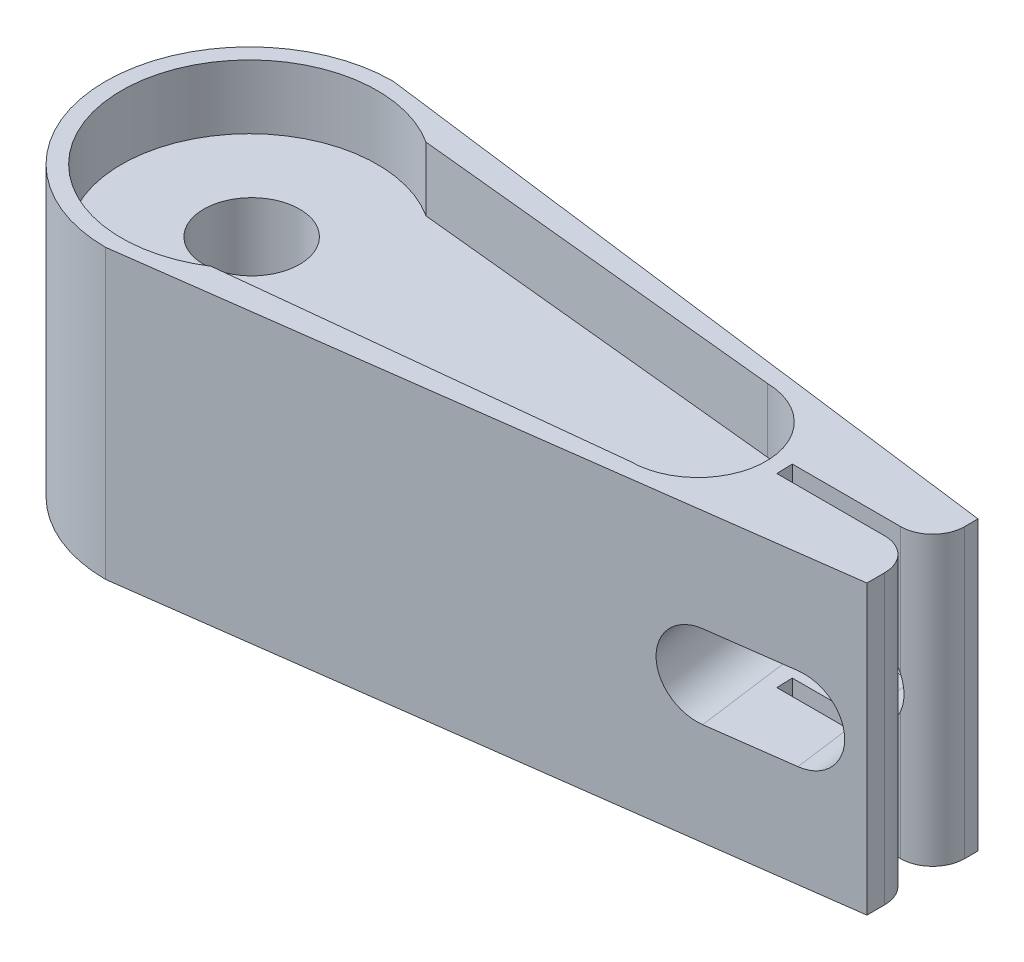
SolidWorks part; units mm, degrees
ref_plane "Front Plane" through (0, 0, 0) normal (0, 0, 1) x (1, 0, 0)
ref_plane "Top Plane" through (0, 0, 0) normal (0, 1, 0) x (1, 0, 0)
ref_plane "Right Plane" through (0, 0, 0) normal (1, 0, 0) x (0, 0, -1)
sketch "Sketch2" plane through (0, 0, 0) normal (0, 1, 0) x (1, 0, 0)
  line L0 (-24.822, 2.75) -> (-24.822, -2.75) construction
  line L1 (-26.9871, 0) -> (-9.8477, 0) construction
  line L2 (-5.9803, -0.2) -> (-5.98, -1.7573)
  line L3 (-5.9802, 0.3) -> (-10.372, 0.3)
  line L4 (-26.9871, 4.4282) -> (-5.9802, 1.719)
  line L5 (-26.9871, -4.5715) -> (-5.98, -1.7573)
  line L6 (-26.9871, 0) -> (-1.9871, 0) construction
  line L7 (-26.9871, -4.5715) -> (-2.3632, -1.0673) construction
  line L8 (-26.9871, 4.4282) -> (-5.9802, 2.3) construction
  line L9 (-10.372, 0.3) -> (-10.3556, -0.2)
  line L10 (-5.98, -1.7573) -> (-5.98, 5.1188) construction
  line L11 (-24.8218, 3.2918) -> (-12.9398, 2.0943)
  line L12 (-12.9872, -2.1664) -> (-24.8217, -3.4351)
  line L13 (-10.3556, -0.2) -> (-5.9803, -0.2)
  line L14 (-5.9802, 0.3) -> (-5.9802, 2.3)
  line L15 (-5.9802, 0.3) -> (-5.9802, -0.3836) construction
  circle A1 centre (-26.9871, 0) radius 1.5
  circle A3 centre (-26.9871, -0.0716) radius 4.4998
  circle A4 centre (-12.9872, -0.0358) radius 2.6366
  circle A6 centre (-12.9872, -0.0358) radius 2.1306
  circle A7 centre (-26.9871, -0.0716) radius 4.0002
  point P5 (-5.9802, -0.9787)
  dimension "D1" = 5.5
  dimension "D3" = 14
  dimension "D4" = 14
  dimension "D5" = 2
  dimension "D9" = 0
  dimension "D10" = 0
  dimension "D6" = 0
extrude "Boss-Extrude1" add sketch "Sketch2" along normal blind 7 contours A7 A1 | A7 L12 A3 L11 | A4 L11 A3 L12 | A6 L11 A4 L12 | A6 region at (-15.571, 0, 0.0394) region at (-19.2555, 0, 0.0535) region at (-24.3629, 0, 3.3143) region at (-12.9872, 0, 0.0358) region at (-30.8741, 0, 0.0717)
extrude "Boss-Extrude2" add sketch "Sketch2<3>" along normal blind 9 contours A7 L11 A3 L4 L5 L12 | A4 L12 A3 L5 | A4 L4 A3 L11 | A6 L12 A4 L9 L11 | A4 L3 L14 L4 | A4 L5 L2 L13 region at (-8.5849, 0, 1.2241) region at (-11.1062, 0, 1.788) region at (-19.5648, 0, 3.2424) region at (-8.6164, 0, -1.2462) region at (-26.4106, 0, 4.3754) region at (-19.5963, 0, -3.1385)
sketch "Sketch2<3>" plane through (0, 0, 0) normal (0, 1, 0) x (1, 0, 0) same geometry as "Sketch2"
fillet "Fillet3" radius 1 2 edges at (-5.9803, 4.5, 0.2) (-5.9802, 4.5, -0.3)
sketch "Sketch3" plane through (0.1258, 0, 0.9394) normal (0.1328, 0, 0.9911) x (0.9911, 0, -0.1328)
  line L0 (-27.3552, 4.5) -> (-6.0777, 4.5) construction
  line L1 (-27.3552, 9) -> (-27.3552, 0) construction
  line L2 (-6.0777, 0) -> (-6.0777, 9) construction
  line L3 (-8.0792, 4.5) -> (-10.7306, 4.5) construction
  line L4 (-8.0792, 3.2) -> (-10.7306, 3.2)
  line L5 (-8.0792, 5.8) -> (-10.7306, 5.8)
  arc A0 (-8.0792, 3.2) -> (-8.0792, 5.8) centre (-8.0792, 4.5) ccw
  arc A1 (-10.7306, 5.8) -> (-10.7306, 3.2) centre (-10.7306, 4.5) ccw
  point P8 (-9.4049, 4.5)
  point P13 (0, 0)
  point P14 (-7.2025, 4.5)
  point P15 (-8.0792, 4.5)
  point P16 (-10.7306, 4.5)
extrude "Cut-Extrude1" cut sketch "Sketch3" against normal through all
